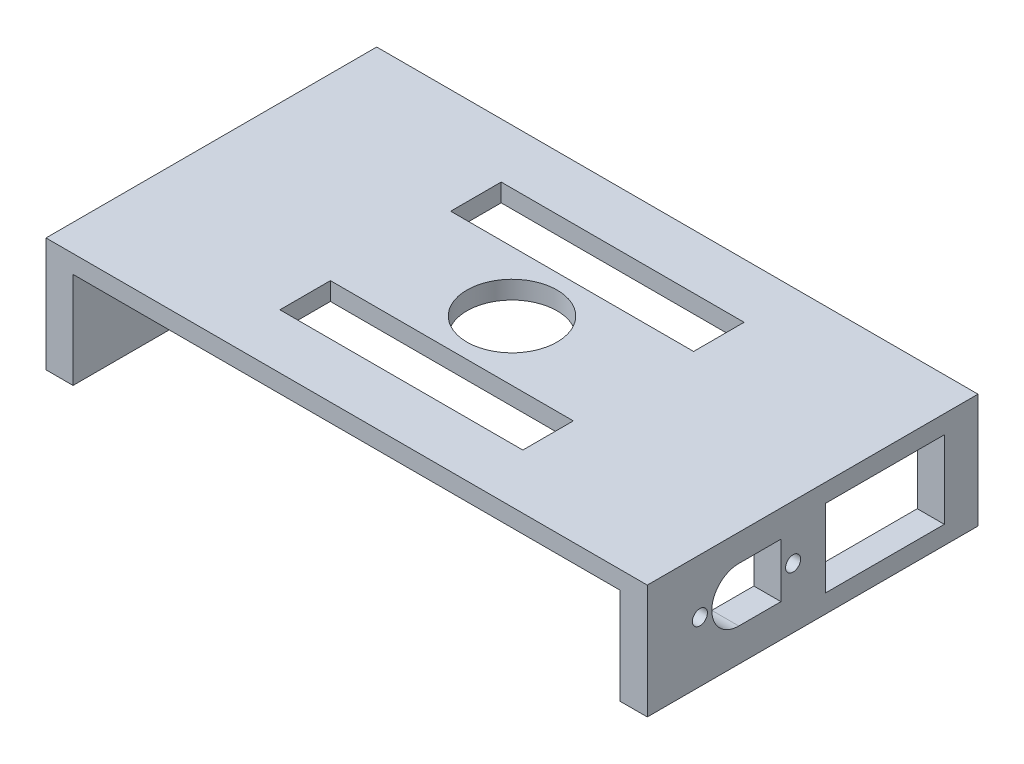
SolidWorks part; units mm, degrees
ref_plane "Front Plane" through (0, 0, 0) normal (0, 0, 1) x (1, 0, 0)
ref_plane "Top Plane" through (0, 0, 0) normal (0, 1, 0) x (1, 0, 0)
ref_plane "Right Plane" through (0, 0, 0) normal (1, 0, 0) x (0, 0, -1)
sketch "Sketch1" plane through (0, 0, 0) normal (0, 1, 0) x (1, 0, 0)
  line L1 (-50, -27.5) -> (50, -27.5)
  line L2 (-50, -27.5) -> (-50, 27.5)
  line L3 (-50, 27.5) -> (50, 27.5)
  line L4 (50, -27.5) -> (50, 27.5)
  line L5 (-50, -27.5) -> (50, 27.5) construction
  line L6 (-50, 27.5) -> (50, -27.5) construction
  point P0 (0, 0)
  dimension "D1" = 100
  dimension "D2" = 55
extrude "Boss-Extrude1" add sketch "Sketch1" along normal blind 19
sketch "Sketch2" plane through (0, 0, 0) normal (0, -1, 0) x (1, 0, 0)
  line L1 (-45.5, -45.5) -> (45.5, -45.5)
  line L2 (-45.5, -45.5) -> (-45.5, 45.5)
  line L3 (-45.5, 45.5) -> (45.5, 45.5)
  line L4 (45.5, -45.5) -> (45.5, 45.5)
  line L5 (-45.5, -45.5) -> (45.5, 45.5) construction
  line L6 (-45.5, 45.5) -> (45.5, -45.5) construction
  point P0 (0, 0)
  dimension "D1" = 91
  dimension "D2" = 91
extrude "Cut-Extrude1" cut sketch "Sketch2" against normal blind 16
sketch "Sketch3" plane through (50, 0, 0) normal (1, 0, 0) x (0, 0, -1)
  line L3 (-5.2727, 5.5) -> (-5.2727, 14.5)
  line L4 (-5.2727, 5.5) -> (-12.2784, 5.5)
  line L9 (-5.2727, 14.5) -> (-12.2784, 14.5)
  arc A1 (-12.2784, 5.5) -> (-12.2784, 14.5) centre (-12.2784, 10) cw
  circle A2 centre (-18.75, 10) radius 1.25
  circle A3 centre (-3.25, 10) radius 1.25
  point P17 (-11, 10)
extrude "Cut-Extrude3" cut sketch "Sketch3" against normal up to next
sketch "Sketch15" plane through (50, 0, 0) normal (1, 0, 0) x (0, 0, -1)
  line L0 (0, 0) -> (0, 19) construction
  line L1 (-27.5, 19) -> (27.5, 19) construction
  line L2 (0, 9.5) -> (12, 9.5) construction
  line L4 (2.1, 3.05) -> (21.9, 3.05)
  line L5 (2.1, 3.05) -> (2.1, 15.95)
  line L6 (2.1, 15.95) -> (21.9, 15.95)
  line L7 (21.9, 3.05) -> (21.9, 15.95)
  line L8 (2.1, 3.05) -> (21.9, 15.95) construction
  line L9 (2.1, 15.95) -> (21.9, 3.05) construction
  dimension "D1" = 12
  dimension "D2" = 19.8
  dimension "D3" = 12.9
extrude "Cut-Extrude13" cut sketch "Sketch15" against normal up to next
sketch "Sketch6" plane through (0, 19, 0) normal (0, 1, 0) x (1, 0, 0)
  line L0 (0, 0) -> (0, -10) construction
  line L1 (20.2, -10) -> (-20.2, -10)
  line L2 (-20.2, -10) -> (-20.2, -18.4)
  line L3 (20.2, -10) -> (20.2, -18.4)
  line L4 (20.2, -18.4) -> (-20.2, -18.4)
  line L5 (0, 0) -> (5, 0) construction
  line L6 (20.2, 10) -> (20.2, 18.4)
  line L7 (20.2, 10) -> (-20.2, 10)
  line L8 (-20.2, 10) -> (-20.2, 18.4)
  line L9 (20.2, 18.4) -> (-20.2, 18.4)
  circle A0 centre (0, 0) radius 7.5
  point P6 (0, -10)
  dimension "D5" = 15
  dimension "D1" = 10
  dimension "D2" = 40.4
  dimension "D3" = 8.4
  dimension "D4" = 5
extrude "Cut-Extrude14" cut sketch "Sketch6" against normal up to next
